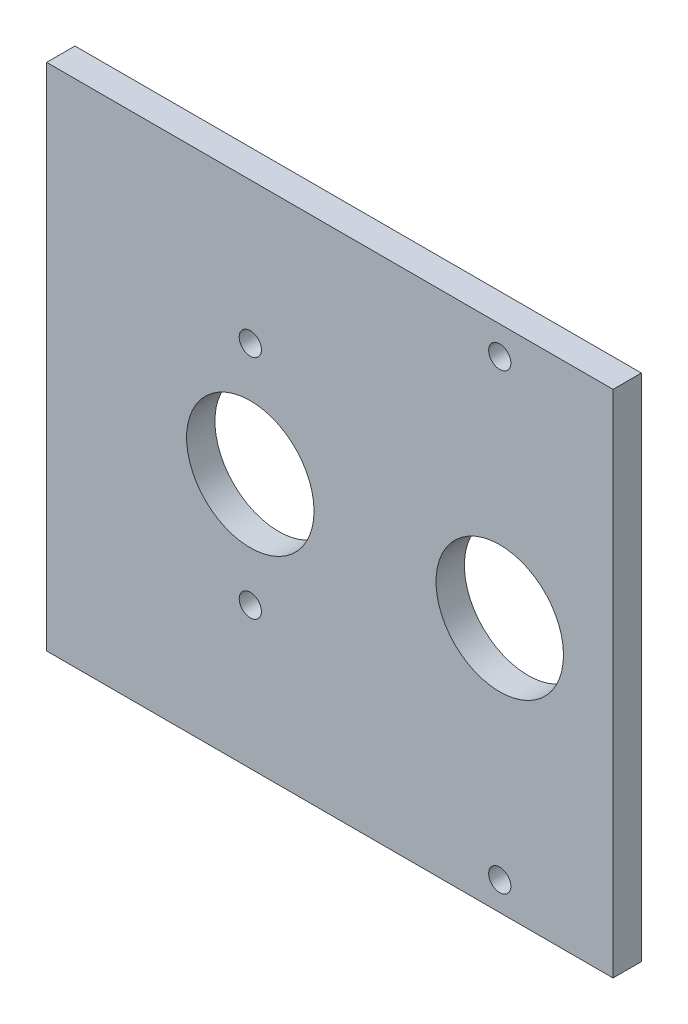
SolidWorks part; units mm, degrees
ref_plane "Front Plane" through (0, 0, 0) normal (0, 0, 1) x (1, 0, 0)
ref_plane "Top Plane" through (0, 0, 0) normal (0, 1, 0) x (1, 0, 0)
ref_plane "Right Plane" through (0, 0, 0) normal (1, 0, 0) x (0, 0, -1)
sketch "Sketch1" plane through (0, 0, 0) normal (0, 0, 1) x (1, 0, 0)
  line L1 (0, 0) -> (127, 0)
  line L2 (0, 0) -> (0, 114.3)
  line L3 (0, 114.3) -> (127, 114.3)
  line L4 (127, 0) -> (127, 114.3)
  circle A0 centre (45.6692, 82.55) radius 2.4892
  circle A1 centre (45.6692, 57.15) radius 14.2875
  circle A2 centre (45.6692, 31.75) radius 2.4892
  circle A3 centre (101.6, 107.95) radius 2.4892
  circle A4 centre (101.6, 57.15) radius 14.2875
  circle A5 centre (101.6, 6.35) radius 2.4892
  dimension "D3" = 25.4
  dimension "D10" = 25.4
  dimension "D12" = 4.9784
  dimension "D13" = 4.9784
  dimension "D14" = 28.575
  dimension "D15" = 28.575
  dimension "D16" = 4.9784
  dimension "D17" = 4.9784
  dimension "D2" = 127
  dimension "D4" = 57.15
  dimension "D5" = 50.8
  dimension "D6" = 50.8
  dimension "D7" = 6.35
  dimension "D8" = 25.4
  dimension "D9" = 25.4
  dimension "D11" = 114.3
  dimension "D18" = 55.9308
extrude "Boss-Extrude1" add sketch "Sketch1" along normal mid plane 6.35
